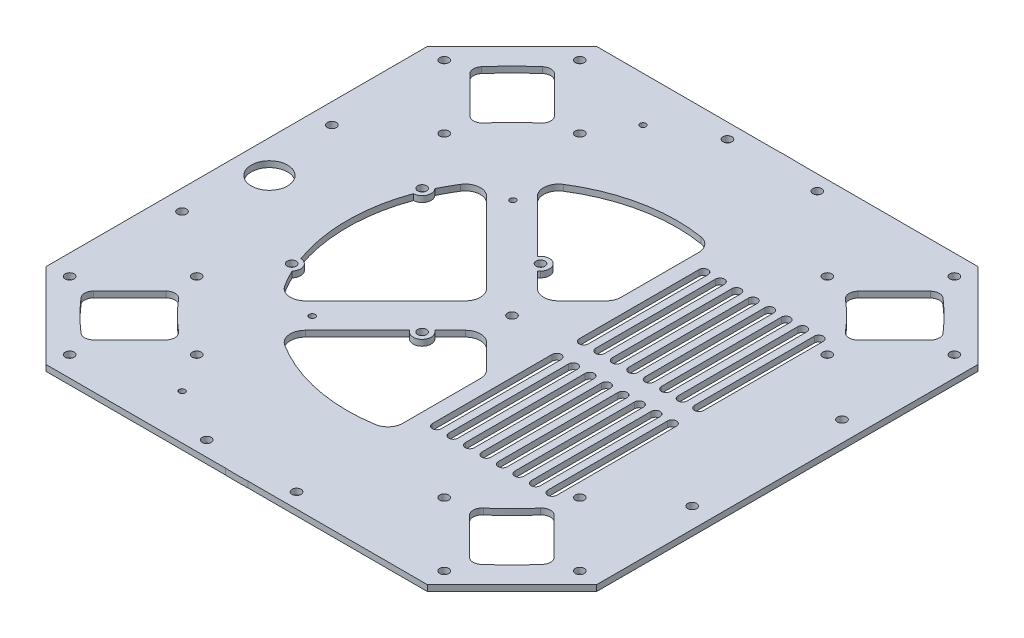
SolidWorks part; units mm, degrees
material "Thornel Mat VMA"
ref_plane "前视基准面" through (0, 0, 0) normal (0, 0, 1) x (1, 0, 0)
ref_plane "上视基准面" through (0, 0, 0) normal (0, 1, 0) x (1, 0, 0)
ref_plane "右视基准面" through (0, 0, 0) normal (1, 0, 0) x (0, 0, -1)
sketch "草图1" plane through (0, 0, 0) normal (0, 1, 0) x (1, 0, 0)
  line L0 (-63.6396, 91.9239) -> (-91.9239, 63.6396)
  line L1 (63.6396, 91.9239) -> (-63.6396, 91.9239)
  line L2 (91.9239, 63.6396) -> (91.9239, -63.6396)
  line L3 (63.6396, -91.9239) -> (-63.6396, -91.9239)
  line L4 (-91.9239, 63.6396) -> (-91.9239, -63.6396)
  line L5 (91.9239, 91.9239) -> (-91.9239, -91.9239) construction
  line L6 (91.9239, -91.9239) -> (-91.9239, 91.9239) construction
  line L7 (91.9239, -63.6396) -> (63.6396, -91.9239)
  line L8 (-91.9239, -63.6396) -> (-63.6396, -91.9239)
  line L9 (63.6396, 91.9239) -> (91.9239, 63.6396)
  line L10 (-91.9239, 91.9239) -> (-91.9239, -91.9239) construction
  line L11 (-91.9239, -91.9239) -> (91.9239, -91.9239) construction
  line L12 (91.9239, -91.9239) -> (91.9239, 91.9239) construction
  line L13 (91.9239, 91.9239) -> (-91.9239, 91.9239) construction
  point P0 (0, 0)
  dimension "D1" = 220
  dimension "D2" = 40
extrude "凸台-拉伸1" add sketch "草图1" along normal blind 2
sketch "草图15" plane through (0, 2, 0) normal (0, 1, 0) x (1, 0, 0)
  line L1 (-40.3412, 82.6837) -> (-31.9185, 62.6852)
  line L2 (44.6358, 80.4465) -> (36.2732, 60.2701)
  line L3 (-42.4295, -81.6317) -> (-34.5316, -61.2845)
  line L4 (41.391, -82.1632) -> (34.5498, -61.2743)
  arc A0 (-42.4295, -81.6317) -> (41.391, -82.1632) centre (0, 0) ccw
  arc A2 (-34.5316, -61.2845) -> (34.5498, -61.2743) centre (0, 0) ccw
  arc A3 (36.2732, 60.2701) -> (-31.9185, 62.6852) centre (0, 0) ccw
  arc A4 (44.6358, 80.4465) -> (-40.3412, 82.6837) centre (0, 0) ccw
  dimension "D1" = 92
extrude "凸台-拉伸3" add sketch "草图15" against normal up to surface (2 mm away) up to face at (0, 0, 0)
sketch "草图18" plane through (0, 2, 0) normal (0, 1, 0) x (1, 0, 0)
  line L0 (-44.0207, 0) -> (12.6253, 0) construction
  line L3 (-54.0207, 0) -> (-91.9239, 0) construction
  line L4 (-91.9239, 63.6396) -> (-91.9239, -63.6396) construction
  line L5 (-4.5, -10) -> (4.5, -10) construction
  line L9 (-4.5, 10) -> (4.5, -10) construction
  line L10 (-4.5, -10) -> (4.5, 10) construction
  line L11 (-4.5, 10) -> (4.5, 10) construction
  circle A9 centre (0, 0) radius 1.5
  point P3 (0, 0)
  point P15 (0, 0)
extrude "切除-拉伸5" cut sketch "草图18" against normal through all both and the other way through all
sketch "草图20" plane through (0, 0, 0) normal (0, -1, 0) x (1, 0, 0)
  line L0 (-45.8783, 0) -> (57.9239, 0) construction
  line L1 (57.9239, 44.5) -> (57.9239, 4.5) construction
  line L2 (59.4239, 44.5) -> (59.4239, 4.5)
  line L3 (56.4239, 44.5) -> (56.4239, 4.5)
  line L4 (57.9239, -44.5) -> (57.9239, -4.5) construction
  line L5 (59.4239, -44.5) -> (59.4239, -4.5)
  line L6 (56.4239, -44.5) -> (56.4239, -4.5)
  line L7 (52.4239, 44.5) -> (52.4239, 4.5) construction
  line L8 (53.9239, 44.5) -> (53.9239, 4.5)
  line L9 (50.9239, 44.5) -> (50.9239, 4.5)
  line L10 (52.4239, -44.5) -> (52.4239, -4.5) construction
  line L11 (53.9239, -44.5) -> (53.9239, -4.5)
  line L12 (50.9239, -44.5) -> (50.9239, -4.5)
  line L13 (46.9239, 44.5) -> (46.9239, 4.5) construction
  line L14 (48.4239, 44.5) -> (48.4239, 4.5)
  line L15 (45.4239, 44.5) -> (45.4239, 4.5)
  line L16 (46.9239, -44.5) -> (46.9239, -4.5) construction
  line L17 (48.4239, -44.5) -> (48.4239, -4.5)
  line L18 (45.4239, -44.5) -> (45.4239, -4.5)
  line L19 (41.4239, 44.5) -> (41.4239, 4.5) construction
  line L20 (42.9239, 44.5) -> (42.9239, 4.5)
  line L21 (39.9239, 44.5) -> (39.9239, 4.5)
  line L22 (41.4239, -44.5) -> (41.4239, -4.5) construction
  line L23 (42.9239, -44.5) -> (42.9239, -4.5)
  line L24 (39.9239, -44.5) -> (39.9239, -4.5)
  line L25 (35.9239, 44.5) -> (35.9239, 4.5) construction
  line L26 (37.4239, 44.5) -> (37.4239, 4.5)
  line L27 (34.4239, 44.5) -> (34.4239, 4.5)
  line L28 (35.9239, -44.5) -> (35.9239, -4.5) construction
  line L29 (37.4239, -44.5) -> (37.4239, -4.5)
  line L30 (34.4239, -44.5) -> (34.4239, -4.5)
  line L31 (30.4239, 44.5) -> (30.4239, 4.5) construction
  line L32 (31.9239, 44.5) -> (31.9239, 4.5)
  line L33 (28.9239, 44.5) -> (28.9239, 4.5)
  line L34 (30.4239, -44.5) -> (30.4239, -4.5) construction
  line L35 (31.9239, -44.5) -> (31.9239, -4.5)
  line L36 (28.9239, -44.5) -> (28.9239, -4.5)
  line L37 (24.9239, 44.5) -> (24.9239, 4.5) construction
  line L38 (26.4239, 44.5) -> (26.4239, 4.5)
  line L39 (23.4239, 44.5) -> (23.4239, 4.5)
  line L40 (24.9239, -44.5) -> (24.9239, -4.5) construction
  line L41 (26.4239, -44.5) -> (26.4239, -4.5)
  line L42 (23.4239, -44.5) -> (23.4239, -4.5)
  line L43 (19.4239, 44.5) -> (19.4239, 4.5) construction
  line L44 (20.9239, 44.5) -> (20.9239, 4.5)
  line L45 (17.9239, 44.5) -> (17.9239, 4.5)
  line L46 (19.4239, -44.5) -> (19.4239, -4.5) construction
  line L47 (20.9239, -44.5) -> (20.9239, -4.5)
  line L48 (17.9239, -44.5) -> (17.9239, -4.5)
  line L49 (91.9239, 63.6396) -> (91.9239, -63.6396) construction
  line L382 (13.9239, -44.5) -> (13.9239, -4.5) construction
  line L383 (12.4239, -44.5) -> (12.4239, -4.5) [skipped]
  line L384 (15.4239, -44.5) -> (15.4239, -4.5) [skipped]
  line L385 (13.9239, 44.5) -> (13.9239, 4.5) construction
  line L386 (15.4239, 44.5) -> (15.4239, 4.5) [skipped]
  line L387 (12.4239, 44.5) -> (12.4239, 4.5) [skipped]
  line L388 (13.9239, -44.5) -> (13.9239, -4.5) construction
  line L389 (12.4239, -44.5) -> (12.4239, -4.5) [skipped]
  line L390 (15.4239, -44.5) -> (15.4239, -4.5) [skipped]
  line L391 (13.9239, 44.5) -> (13.9239, 4.5) construction
  line L392 (15.4239, 44.5) -> (15.4239, 4.5) [skipped]
  line L393 (12.4239, 44.5) -> (12.4239, 4.5) [skipped]
  arc A0 (59.4239, 44.5) -> (56.4239, 44.5) centre (57.9239, 44.5) ccw
  arc A1 (56.4239, 4.5) -> (59.4239, 4.5) centre (57.9239, 4.5) ccw
  arc A2 (59.4239, -44.5) -> (56.4239, -44.5) centre (57.9239, -44.5) cw
  arc A3 (56.4239, -4.5) -> (59.4239, -4.5) centre (57.9239, -4.5) cw
  arc A4 (53.9239, 44.5) -> (50.9239, 44.5) centre (52.4239, 44.5) ccw
  arc A5 (50.9239, 4.5) -> (53.9239, 4.5) centre (52.4239, 4.5) ccw
  arc A6 (53.9239, -44.5) -> (50.9239, -44.5) centre (52.4239, -44.5) cw
  arc A7 (50.9239, -4.5) -> (53.9239, -4.5) centre (52.4239, -4.5) cw
  arc A8 (48.4239, 44.5) -> (45.4239, 44.5) centre (46.9239, 44.5) ccw
  arc A9 (45.4239, 4.5) -> (48.4239, 4.5) centre (46.9239, 4.5) ccw
  arc A10 (48.4239, -44.5) -> (45.4239, -44.5) centre (46.9239, -44.5) cw
  arc A11 (45.4239, -4.5) -> (48.4239, -4.5) centre (46.9239, -4.5) cw
  arc A12 (42.9239, 44.5) -> (39.9239, 44.5) centre (41.4239, 44.5) ccw
  arc A13 (39.9239, 4.5) -> (42.9239, 4.5) centre (41.4239, 4.5) ccw
  arc A14 (42.9239, -44.5) -> (39.9239, -44.5) centre (41.4239, -44.5) cw
  arc A15 (39.9239, -4.5) -> (42.9239, -4.5) centre (41.4239, -4.5) cw
  arc A16 (37.4239, 44.5) -> (34.4239, 44.5) centre (35.9239, 44.5) ccw
  arc A17 (34.4239, 4.5) -> (37.4239, 4.5) centre (35.9239, 4.5) ccw
  arc A18 (37.4239, -44.5) -> (34.4239, -44.5) centre (35.9239, -44.5) cw
  arc A19 (34.4239, -4.5) -> (37.4239, -4.5) centre (35.9239, -4.5) cw
  arc A20 (31.9239, 44.5) -> (28.9239, 44.5) centre (30.4239, 44.5) ccw
  arc A21 (28.9239, 4.5) -> (31.9239, 4.5) centre (30.4239, 4.5) ccw
  arc A22 (31.9239, -44.5) -> (28.9239, -44.5) centre (30.4239, -44.5) cw
  arc A23 (28.9239, -4.5) -> (31.9239, -4.5) centre (30.4239, -4.5) cw
  arc A24 (26.4239, 44.5) -> (23.4239, 44.5) centre (24.9239, 44.5) ccw
  arc A25 (23.4239, 4.5) -> (26.4239, 4.5) centre (24.9239, 4.5) ccw
  arc A26 (26.4239, -44.5) -> (23.4239, -44.5) centre (24.9239, -44.5) cw
  arc A27 (23.4239, -4.5) -> (26.4239, -4.5) centre (24.9239, -4.5) cw
  arc A28 (20.9239, 44.5) -> (17.9239, 44.5) centre (19.4239, 44.5) ccw
  arc A29 (17.9239, 4.5) -> (20.9239, 4.5) centre (19.4239, 4.5) ccw
  arc A30 (20.9239, -44.5) -> (17.9239, -44.5) centre (19.4239, -44.5) cw
  arc A31 (17.9239, -4.5) -> (20.9239, -4.5) centre (19.4239, -4.5) cw
  arc A258 (12.4239, -44.5) -> (15.4239, -44.5) centre (13.9239, -44.5) ccw [skipped]
  arc A259 (15.4239, -4.5) -> (12.4239, -4.5) centre (13.9239, -4.5) ccw [skipped]
  arc A260 (15.4239, 44.5) -> (12.4239, 44.5) centre (13.9239, 44.5) ccw [skipped]
  arc A261 (12.4239, 4.5) -> (15.4239, 4.5) centre (13.9239, 4.5) ccw [skipped]
  point P5 (57.9239, 24.5)
  point P11 (57.9239, 3)
  point P13 (57.9239, -24.5)
  point P18 (57.9239, -3)
  point P19 (79.1207, 0)
  point P23 (52.4239, 24.5)
  point P29 (52.4239, 3)
  point P31 (52.4239, -24.5)
  point P36 (52.4239, -3)
  point P39 (46.9239, 24.5)
  point P45 (46.9239, 3)
  point P47 (46.9239, -24.5)
  point P52 (46.9239, -3)
  point P55 (41.4239, 24.5)
  point P61 (41.4239, 3)
  point P63 (41.4239, -24.5)
  point P68 (41.4239, -3)
  point P71 (35.9239, 24.5)
  point P77 (35.9239, 3)
  point P79 (35.9239, -24.5)
  point P84 (35.9239, -3)
  point P87 (30.4239, 24.5)
  point P93 (30.4239, 3)
  point P95 (30.4239, -24.5)
  point P100 (30.4239, -3)
  point P103 (24.9239, 24.5)
  point P109 (24.9239, 3)
  point P111 (24.9239, -24.5)
  point P116 (24.9239, -3)
  point P119 (19.4239, 24.5)
  point P125 (19.4239, 3)
  point P127 (19.4239, -24.5)
  point P132 (19.4239, -3)
  point P135 (21.0655, -24.0622)
  point P140 (13.9239, -3)
  point P142 (13.9239, 3)
  point P149 (21.0655, 24.0622)
  point P157 (21.0655, -24.0622)
  point P164 (21.0655, 24.0622)
  point P171 (21.0655, -24.0622)
  point P178 (21.0655, 24.0622)
  point P185 (21.0655, -24.0622)
  point P192 (21.0655, 24.0622)
  point P199 (21.0655, -24.0622)
  point P206 (21.0655, 24.0622)
  point P213 (21.0655, -24.0622)
  point P220 (21.0655, 24.0622)
  point P227 (16.1207, -24.0622)
  point P234 (16.1207, 24.0622)
  point P241 (16.1207, -24.0622)
  point P248 (16.1207, 24.0622)
  point P255 (11.1207, -24.0622)
  point P262 (11.1207, 24.0622)
  point P269 (11.1207, -24.0622)
  point P276 (11.1207, 24.0622)
  point P283 (11.1207, -29.0622)
  point P290 (11.1207, 29.0622)
  point P297 (11.1207, -29.0622)
  point P304 (11.1207, 29.0622)
  point P311 (15.1207, -29)
  point P318 (15.1207, 29)
  point P325 (15.1207, -29)
  point P332 (15.1207, 29)
  point P339 (15.1207, -24)
  point P346 (15.1207, 24)
  point P353 (15.1207, -24)
  point P360 (15.1207, 24)
  point P367 (15.1207, -24.5)
  point P374 (15.1207, 24.5)
  point P381 (15.1207, -24.5)
  point P388 (15.1207, 24.5)
  point P395 (15.1207, -24.5)
  point P402 (15.1207, 24.5)
  point P409 (15.1207, -24.5)
  point P416 (15.1207, 24.5)
  point P423 (15.1207, -24.5)
  point P430 (15.1207, 24.5)
  point P437 (15.1207, -24.5)
  point P444 (15.1207, 24.5)
  point P451 (15.1207, -24.5)
  point P458 (15.1207, 24.5)
  point P465 (15.1207, -24.5)
  point P472 (15.1207, 24.5)
  point P479 (15.1207, -24.5)
  point P486 (15.1207, 24.5)
  point P493 (15.1207, -24.5)
  point P500 (15.1207, 24.5)
  point P507 (15.1207, -24.5)
  point P514 (15.1207, 24.5)
  point P521 (15.1207, -24.5)
  point P528 (15.1207, 24.5)
  point P535 (15.1207, -24.5)
  point P542 (15.1207, 24.5)
  point P549 (15.1207, -24.5)
  point P556 (15.1207, 24.5)
  point P563 (15.1207, -24.5)
  point P570 (15.1207, 24.5)
  point P577 (15.1207, -24.5)
  point P584 (15.1207, 24.5)
  point P591 (15.1207, -24.5)
  point P598 (15.1207, 24.5)
  point P605 (15.1207, -24.5)
  point P612 (15.1207, 24.5)
  point P619 (15.1207, -24.5)
  point P626 (15.1207, 24.5)
  point P633 (15.1207, -24.5)
  point P640 (15.1207, 24.5)
  point P647 (15.1207, -24.5)
  point P654 (15.1207, 24.5)
  point P661 (15.1207, -24.5)
  point P668 (15.1207, 24.5)
  point P675 (15.1207, -24.5)
  point P682 (15.1207, 24.5)
  point P689 (15.1207, -24.5)
  point P696 (15.1207, 24.5)
  point P703 (15.1207, -24.5)
  point P710 (15.1207, 24.5)
  point P717 (15.1207, -24.5)
  point P724 (15.1207, 24.5)
  point P731 (15.1207, -24.5)
  point P738 (15.1207, 24.5)
  point P745 (15.1207, -24.5)
  point P752 (15.1207, 24.5)
  point P759 (15.1207, -24.5)
  point P766 (15.1207, 24.5)
  point P773 (15.1207, -24.5)
  point P780 (15.1207, 24.5)
  point P787 (15.1207, -24.5)
  point P794 (15.1207, 24.5)
  point P801 (15.1207, -24.5)
  point P808 (15.1207, 24.5)
  point P815 (14.4239, -24.5)
  point P822 (14.4239, 24.5)
  point P829 (14.4239, -24.5)
  point P836 (14.4239, 24.5)
  point P843 (13.9239, -24.5)
  point P850 (13.9239, 24.5)
  point P857 (13.9239, -24.5)
  point P864 (13.9239, 24.5)
  point P871 (13.9239, -24.5)
  point P878 (13.9239, 24.5)
  point P885 (13.9239, -24.5)
  point P892 (13.9239, 24.5)
  point P899 (13.9239, -24.5)
  point P906 (13.9239, 24.5)
  point P913 (13.9239, -24.5)
  point P920 (13.9239, 24.5)
  point P927 (13.9239, -24.5)
  point P934 (13.9239, 24.5)
  dimension "D2" = 9
  dimension "D5" = 1.5
  dimension "D1" = 3
  dimension "D3" = 40
  dimension "D4" = 34
  dimension "D6" = 5.5
extrude "切除-拉伸7" cut sketch "草图20" against normal through all both and the other way through all
hole_wizard "孔1" positions "草图27" profile "草图28" legacy end condition through all
sketch "草图27" plane through (0, 2, 0) normal (0, 1, 0) x (1, 0, 0)
  point P0 (-85.1534, 62.5296)
  point P3 (-63.9402, 41.3164)
  point P6 (-62.5259, 85.157)
  point P9 (-41.3127, 63.9438)
  point P12 (41.3127, 63.9438)
  point P15 (62.5259, 85.157)
  point P18 (85.1534, 62.5296)
  point P21 (63.9402, 41.3164)
  point P24 (63.9402, -41.3091)
  point P27 (85.1534, -62.5223)
  point P36 (62.5259, -85.1497)
  point P39 (41.3127, -63.9365)
  point P42 (-85.1534, -62.5223)
  point P45 (-63.9402, -41.3091)
  point P48 (-41.3127, -63.9365)
  point P51 (-62.5259, -85.1497)
sketch "草图28" plane through (-85.1534, 2, -62.5296) normal (1, 0, 0) x (0, 0, 1)
  line L0 (0, 0) -> (0, 2)
  line L1 (0, 2) -> (1.5, 2)
  line L2 (1.5, 2) -> (1.5, 0)
  line L3 (1.5, 0) -> (0, 0)
  line L4 (0, 110) -> (0, -10) construction
  dimension "直径" = 3
  dimension "深度" = 2
sketch "草图31" plane through (0, 2, 0) normal (0, 1, 0) x (1, 0, 0)
  line L0 (-62.7269, 76.9258) -> (-50.6692, 64.8681)
  line L1 (-50.7195, 64.8107) -> (-62.7268, 76.9107) construction
  line L2 (-76.8731, 62.7876) -> (-64.8163, 50.7308)
  line L3 (-76.8882, 62.7878) -> (-64.8737, 50.6805) construction
  line L4 (76.9258, 62.7269) -> (64.8681, 50.6692)
  line L5 (62.7876, 76.8731) -> (50.7308, 64.8163)
  line L6 (62.7269, -76.9258) -> (50.6692, -64.8681)
  line L7 (76.8731, -62.7876) -> (64.8163, -50.7308)
  line L8 (-76.9258, -62.7269) -> (-64.8681, -50.6692)
  line L9 (-62.7876, -76.8731) -> (-50.7308, -64.8163)
  line L10 (41.3127, 63.9438) -> (62.5259, 85.157) construction
  arc A0 (-66.8133, 77.0713) -> (-77.017, 66.8759) centre (0, 0) ccw
  arc A1 (-50.8592, 60.4512) -> (-60.4012, 50.9185) centre (0, 0) ccw
  arc A2 (-62.7269, 76.9258) -> (-66.8133, 77.0713) centre (-64.8482, 74.8045) ccw
  arc A3 (-50.8592, 60.4512) -> (-50.6692, 64.8681) centre (-52.7905, 62.7468) ccw
  arc A4 (-60.4012, 50.9185) -> (-64.8163, 50.7308) centre (-62.695, 52.8521) cw
  arc A5 (-76.8731, 62.7876) -> (-77.017, 66.8759) centre (-74.7518, 64.9089) cw
  arc A6 (77.0713, 66.8133) -> (66.8759, 77.017) centre (0, 0) ccw
  arc A7 (60.4512, 50.8592) -> (50.9185, 60.4012) centre (0, 0) ccw
  arc A8 (76.9258, 62.7269) -> (77.0713, 66.8133) centre (74.8045, 64.8482) ccw
  arc A9 (60.4512, 50.8592) -> (64.8681, 50.6692) centre (62.7468, 52.7905) ccw
  arc A10 (50.9185, 60.4012) -> (50.7308, 64.8163) centre (52.8521, 62.695) cw
  arc A11 (62.7876, 76.8731) -> (66.8759, 77.017) centre (64.9089, 74.7518) cw
  arc A12 (66.8133, -77.0713) -> (77.017, -66.8759) centre (0, 0) ccw
  arc A13 (50.8592, -60.4512) -> (60.4012, -50.9185) centre (0, 0) ccw
  arc A14 (62.7269, -76.9258) -> (66.8133, -77.0713) centre (64.8482, -74.8045) ccw
  arc A15 (50.8592, -60.4512) -> (50.6692, -64.8681) centre (52.7905, -62.7468) ccw
  arc A16 (60.4012, -50.9185) -> (64.8163, -50.7308) centre (62.695, -52.8521) cw
  arc A17 (76.8731, -62.7876) -> (77.017, -66.8759) centre (74.7518, -64.9089) cw
  arc A18 (-77.0713, -66.8133) -> (-66.8759, -77.017) centre (0, 0) ccw
  arc A19 (-60.4512, -50.8592) -> (-50.9185, -60.4012) centre (0, 0) ccw
  arc A20 (-76.9258, -62.7269) -> (-77.0713, -66.8133) centre (-74.8045, -64.8482) ccw
  arc A21 (-60.4512, -50.8592) -> (-64.8681, -50.6692) centre (-62.7468, -52.7905) ccw
  arc A22 (-50.9185, -60.4012) -> (-50.7308, -64.8163) centre (-52.8521, -62.695) cw
  arc A23 (-62.7876, -76.8731) -> (-66.8759, -77.017) centre (-64.9089, -74.7518) cw
  point P13 (-64.6752, 78.8741)
  point P20 (-78.823, 64.7375)
  point P22 (-60.4087, -50.9097)
  point P59 (0, 0)
  dimension "D1" = 3
  dimension "D3" = 102
  dimension "D4" = 79
  dimension "D2" = 4
extrude "切除-拉伸14" cut sketch "草图31" against normal through all both and the other way through all
sketch "草图32" plane through (0, 2, 0) normal (0, 1, 0) x (1, 0, 0)
  circle A0 centre (-80.9686, 0) radius 6.05
  circle A1 centre (-80.9686, 0) radius 6.05 construction
extrude "切除-拉伸15" cut sketch "草图32" against normal through all both and the other way through all
hole_wizard "孔3" positions "草图34" profile "草图35" legacy end condition through all
sketch "草图34" plane through (0, 2, 0) normal (0, 1, 0) x (1, 0, 0)
  circle A0 centre (85.1534, -25) radius 1.5 construction
  circle A1 centre (85.1534, 25) radius 1.5 construction
  circle A2 centre (-85.1534, -25) radius 1.5 construction
  circle A3 centre (-85.1534, 25) radius 1.5 construction
  point P0 (-85.1534, 25)
  point P2 (-85.1534, -25)
  point P4 (-15, 86.9239)
  point P6 (15, 86.9239)
  point P8 (85.1534, 25)
  point P10 (85.1534, -25)
  point P12 (-15, -86.9239)
  point P14 (15, -86.9239)
  point P17 (0, 0)
  point P20 (0, 0)
  point P23 (0, 0)
  point P26 (0, 0)
sketch "草图35" plane through (-85.1534, 2, -25) normal (1, 0, 0) x (0, 0, 1)
  line L0 (0, 0) -> (0, 2)
  line L1 (0, 2) -> (1.5, 2)
  line L2 (1.5, 2) -> (1.5, 0)
  line L3 (1.5, 0) -> (0, 0)
  line L4 (0, 110) -> (0, -10) construction
  dimension "直径" = 3
  dimension "深度" = 2
sketch "草图36" plane through (0, 2, 0) normal (0, 1, 0) x (1, 0, 0)
  line L1 (-4.2426, -4.2426) -> (0, 0) construction
  line L2 (11.4594, -19.9447) -> (3.5355, -12.0208)
  line L6 (0, 0) -> (-34.4161, 42.9014) construction
  line L7 (-42.9014, 34.4161) -> (0, 0) construction
  line L8 (3.5355, 12.0208) -> (11.4594, 19.9447)
  line L9 (-8.4853, 0) -> (0, -8.4853) construction
  line L10 (0, -8.4853) -> (8.4853, 0) construction
  line L11 (8.4853, 0) -> (0, 8.4853) construction
  line L12 (0, 0) -> (-42.9014, -34.4161) construction
  line L13 (0, 0) -> (-34.4161, -42.9014) construction
  line L14 (-12.0208, -3.5355) -> (-38.7318, -30.2465)
  line L15 (-12.0208, 3.5355) -> (-38.7318, 30.2465)
  line L16 (-3.5355, 12.0208) -> (-30.2465, 38.7318)
  line L17 (12.9239, 49.3681) -> (12.9239, 23.4802)
  line L18 (12.9239, -23.4802) -> (12.9239, -49.3681)
  line L19 (-3.5355, -12.0208) -> (-30.2465, -38.7318)
  line L20 (17.9239, 4.5) -> (17.9239, 44.5) construction
  line L21 (-8.4853, 0) -> (0, 8.4853) construction
  line L22 (-8.4853, 0) -> (8.4853, 0) construction
  line L23 (0, 8.4853) -> (0, -8.4853) construction
  arc A0 (8.7163, 54.3049) -> (-29.382, 46.494) centre (0, 0) ccw
  arc A1 (-46.494, 29.382) -> (-46.494, -29.382) centre (0, 0) ccw
  arc A2 (12.9239, -49.3681) -> (8.7163, -54.3049) centre (7.9239, -49.3681) cw
  arc A3 (-29.382, -46.494) -> (-30.2465, -38.7318) centre (-26.711, -42.2673) cw
  arc A4 (-38.7318, -30.2465) -> (-46.494, -29.382) centre (-42.2673, -26.711) cw
  arc A5 (-38.7318, 30.2465) -> (-46.494, 29.382) centre (-42.2673, 26.711) ccw
  arc A6 (-29.382, -46.494) -> (8.7163, -54.3049) centre (0, 0) ccw
  arc A7 (12.9239, 49.3681) -> (8.7163, 54.3049) centre (7.9239, 49.3681) ccw
  arc A8 (-30.2465, 38.7318) -> (-29.382, 46.494) centre (-26.711, 42.2673) cw
  arc A9 (12.9239, -23.4802) -> (11.4594, -19.9447) centre (7.9239, -23.4802) ccw
  arc A10 (11.4594, 19.9447) -> (12.9239, 23.4802) centre (7.9239, 23.4802) ccw
  arc A11 (3.5355, -12.0208) -> (-3.5355, -12.0208) centre (0, -15.5563) ccw
  arc A12 (-12.0208, -3.5355) -> (-12.0208, 3.5355) centre (-15.5563, 0) ccw
  arc A13 (3.5355, 12.0208) -> (-3.5355, 12.0208) centre (0, 15.5563) cw
  point P1 (-4.2426, -4.2426)
  point P4 (0, 0)
  point P10 (0, 0)
  point P40 (12.9239, 21.4092)
  dimension "D1" = 110
  dimension "D4" = 5
  dimension "D2" = 12
  dimension "D3" = 5
extrude "切除-拉伸16" cut sketch "草图36" against normal blind 10
hole_wizard "孔4" positions "草图38" profile "草图39" legacy end condition through all
sketch "草图38" plane through (0, 2, 0) normal (0, 1, 0) x (1, 0, 0)
  line L0 (0, 0) -> (-33.1949, 0) construction
  line L2 (-33.1949, 33.5) -> (-33.1949, -33.5) construction
  line L4 (-28.1949, 21.1762) -> (-28.1949, 95.1762) construction
  line L5 (-3.7417, 91.9239) -> (-63.6396, 91.9239) construction
  line L6 (-63.6396, -91.9239) -> (-3.7417, -91.9239) construction
  point P5 (-33.1949, 33.5)
  point P6 (-33.1949, -33.5)
  point P15 (-33.1949, 76.9239)
  point P17 (-33.1949, -76.9239)
  point P21 (-33.1949, -79.1058)
  point P22 (-33.1949, 72.1124)
  dimension "D1" = 5
  dimension "D2" = 67
  dimension "D3" = 15
  dimension "D4" = 15
sketch "草图39" plane through (-33.1949, 2, 76.9239) normal (1, 0, 0) x (0, 0, 1)
  line L0 (0, 0) -> (0, 2)
  line L1 (0, 2) -> (1, 2)
  line L2 (1, 2) -> (1, 0)
  line L3 (1, 0) -> (0, 0)
  line L4 (0, 110) -> (0, -10) construction
  dimension "直径" = 2
  dimension "深度" = 2
sketch "草图40" plane through (0, 2, 0) normal (0, 1, 0) x (1, 0, 0)
  line L0 (-52.6274, 22.6274) -> (-49.3406, 19.3406) construction
  line L1 (-12.1456, 17.8544) -> (-6.2766, 23.7234) construction
  line L2 (-12.3577, 21.885) -> (-14.1806, 20.062)
  line L3 (-9.4939, 24.7487) -> (-14.3933, 19.8493) construction
  line L4 (-14.1806, 20.062) -> (-12.2509, 15.8501)
  line L5 (-12.2509, 15.8501) -> (-9.162, 16.5953)
  line L6 (-10.1507, 15.6067) -> (-5.2513, 20.5061) construction
  line L7 (-9.162, 16.5953) -> (-8.115, 17.6423)
  line L8 (0, 0) -> (-55, 0) construction
  line L9 (-12.1456, -17.8544) -> (-6.2766, -23.7234) construction
  line L10 (-52.6274, -22.6274) -> (-49.3406, -19.3406) construction
  line L11 (-9.162, -16.5953) -> (-8.115, -17.6423)
  line L12 (-12.2509, -15.8501) -> (-9.162, -16.5953)
  line L13 (-14.1806, -20.062) -> (-12.2509, -15.8501)
  line L14 (-12.3577, -21.885) -> (-14.1806, -20.062)
  arc A0 (-51.5314, 23.7234) -> (-53.7234, 21.5314) centre (-52.6274, 22.6274) ccw construction
  circle A1 centre (-51.7789, 21.7789) radius 3
  arc A2 (-12.1456, 20.0465) -> (-9.9535, 17.8544) centre (-11.0495, 18.9505) ccw construction
  arc A3 (-6.2766, 21.5314) -> (-8.4686, 23.7234) centre (-7.3726, 22.6274) ccw construction
  arc A4 (-8.115, 17.6423) -> (-12.3577, 21.885) centre (-10.2364, 19.7636) ccw
  arc A5 (-46.494, 29.382) -> (-46.494, -29.382) centre (0, 0) ccw construction
  arc A6 (-8.115, -17.6423) -> (-12.3577, -21.885) centre (-10.2364, -19.7636) cw
  circle A7 centre (-51.7789, -21.7789) radius 3
  dimension "D1" = 6
  dimension "D2" = 1.2
  dimension "D3" = 2.7
extrude "凸台-拉伸4" add sketch "草图40" against normal blind 2
hole_wizard "孔5" positions "草图41" profile "草图42" legacy end condition through all
sketch "草图41" plane through (0, 2, 0) normal (0, 1, 0) x (1, 0, 0)
  line L0 (-55, 0) -> (0, 0) construction
  arc A0 (-51.6944, 18.7801) -> (-49.5763, 23.8157) centre (-51.7789, 21.7789) ccw construction
  arc A1 (-8.115, 17.6423) -> (-12.3577, 21.885) centre (-10.2364, 19.7636) ccw construction
  arc A2 (-51.6944, 18.7801) -> (-51.6944, -18.7801) centre (0, 0) ccw construction
  point P0 (-51.7789, 21.7789)
  point P9 (-10.2364, 19.7636)
  point P23 (-10.2364, -19.7636)
  point P24 (-51.7789, -21.7789)
sketch "草图42" plane through (-51.7789, 2, -21.7789) normal (1, 0, 0) x (0, 0, 1)
  line L0 (0, 0) -> (0, 2)
  line L1 (0, 2) -> (1.5, 2)
  line L2 (1.5, 2) -> (1.5, 0)
  line L3 (1.5, 0) -> (0, 0)
  line L4 (0, 110) -> (0, -10) construction
  dimension "直径" = 3
  dimension "深度" = 2
